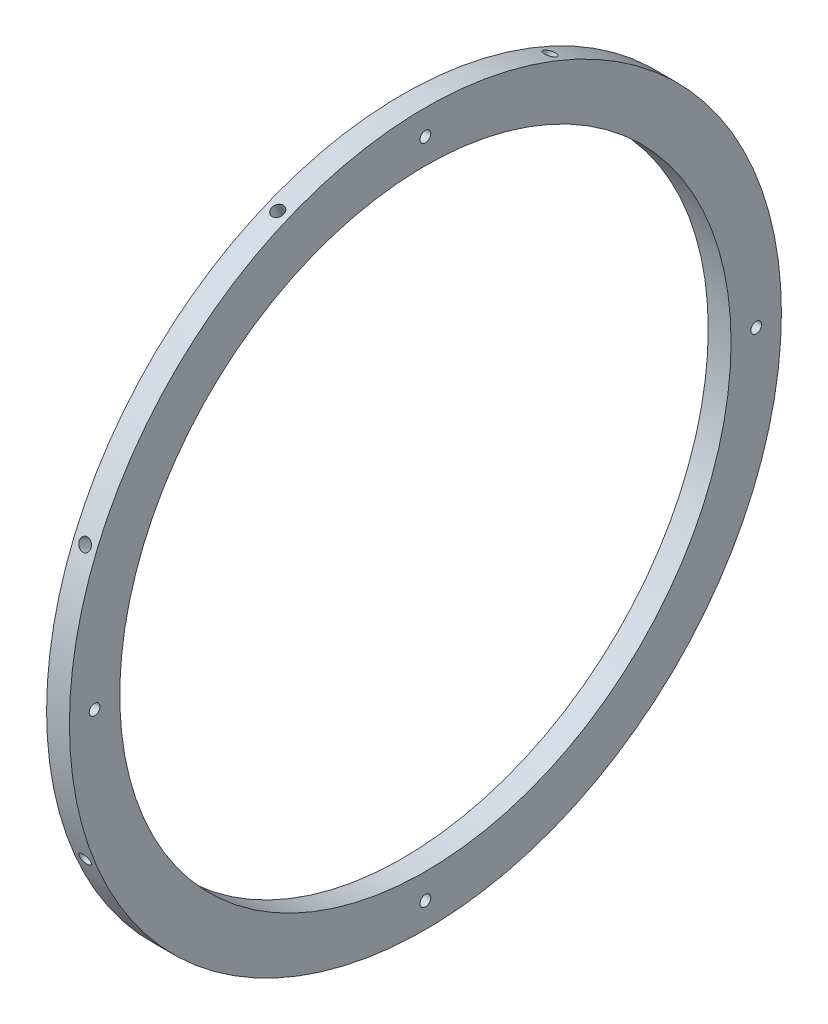
SolidWorks part; units mm, degrees
ref_plane "Front Plane" through (0, 0, 0) normal (0, 0, 1) x (1, 0, 0)
ref_plane "Top Plane" through (0, 0, 0) normal (0, 1, 0) x (1, 0, 0)
ref_plane "Right Plane" through (0, 0, 0) normal (1, 0, 0) x (0, 0, -1)
sketch "Ring Sketch" plane through (0, 0, 0) normal (1, 0, 0) x (0, 0, -1)
  circle A0 centre (0, 0) radius 99
  circle A1 centre (0, 0) radius 85
  circle A2 centre (0, 92) radius 1.5
  circle A3 centre (-92, 0) radius 1.5
  circle A4 centre (0, -92) radius 1.5
  circle A5 centre (92, 0) radius 1.5
extrude "Ring" add sketch "Ring Sketch" along normal blind 6.35 from offset 3.18
ref_axis "Engine Axis" through (9.8475, 0, 0) along (-1, 0, 0)
ref_plane "Clock Plane 22.5" through (0, 0, 0) normal (0, -0.9239, -0.3827) x (-1, 0, 0)
sketch "Wall Screw Holes Sketch" plane through (0, 0, 0) normal (0, -0.9239, -0.3827) x (-1, 0, 0)
  circle A0 centre (-6.355, 0) radius 1.65
extrude "Wall Screw Holes" cut sketch "Wall Screw Holes Sketch" against normal blind 9 from offset 91 offset against normal yes
pattern_circular "Wall Screw Holes x8" count 8 over 360 about axis through (9.8475, 0, 0) along (-1, 0, 0) of "Wall Screw Holes"
